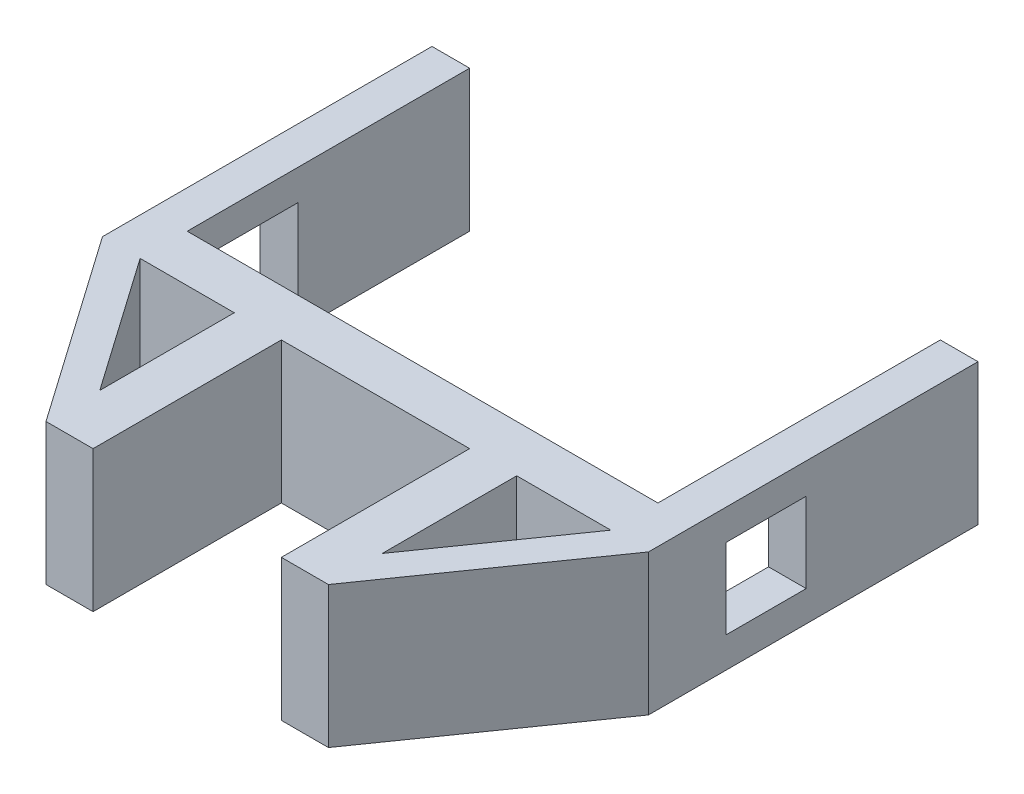
SolidWorks part; units mm, degrees
ref_plane "Front Plane" through (0, 0, 0) normal (0, 0, 1) x (1, 0, 0)
ref_plane "Top Plane" through (0, 0, 0) normal (0, 1, 0) x (1, 0, 0)
ref_plane "Right Plane" through (0, 0, 0) normal (1, 0, 0) x (0, 0, -1)
ref_axis "X" through (-88.99, 0, 0) along (1, 0, 0)
ref_axis "Y" through (0, 55, 0) along (0, -1, 0)
ref_axis "Z" through (0, 0, -88.99) along (0, 0, 1)
sketch "Sketch1" plane through (0, 0, 0) normal (0, 1, 0) x (1, 0, 0)
  line L0 (-50, 0) -> (50, 0)
  line L1 (50, 0) -> (50, 60)
  line L2 (50, 60) -> (58, 60)
  line L3 (58, 60) -> (58, -10)
  line L4 (58, -10) -> (30, -10)
  line L5 (30, -10) -> (30, -50)
  line L6 (30, -50) -> (20, -50)
  line L7 (20, -50) -> (20, -10)
  line L8 (20, -10) -> (-20, -10)
  line L9 (0, 0) -> (0, -10) construction
  line L10 (58, -10) -> (30, -50)
  line L11 (30, -38.5714) -> (50, -10)
  line L12 (-30, -38.5714) -> (-50, -10)
  line L13 (-58, -10) -> (-30, -50)
  line L14 (-20, -50) -> (-20, -10)
  line L15 (-30, -50) -> (-20, -50)
  line L16 (-30, -10) -> (-30, -50)
  line L17 (-58, -10) -> (-30, -10)
  line L18 (-58, 60) -> (-58, -10)
  line L19 (-50, 60) -> (-58, 60)
  line L20 (-50, 0) -> (-50, 60)
  point P15 (71.9459, -19.7642)
  point P16 (24.7333, -18.5818)
  point P17 (27.6346, -21.3468)
  point P28 (30.7968, -16.7781)
  point P29 (24.4198, -91.0008)
  dimension "D1" = 50
  dimension "D2" = 40
  dimension "D3" = 8
  dimension "D4" = 10
  dimension "D5" = 10
  dimension "D6" = 60
  dimension "D7" = 116
  dimension "D8" = 110
  dimension "D9" = 40
extrude "Boss-Extrude1" add sketch "Sketch1" along normal mid plane 30 contours L0 L9 L8 L7 L6 L5 L4 L3 L2 L1 | L9 L0 L20 L19 L18 L17 L16 L15 L14 L8 | L11 L5 L10 L4 | L17 L13 L16 L12 region at (-36.1233, 0, 0.3425) region at (36.1233, 0, 0.3425) region at (-42.1111, 0, 27.3016) region at (42.1111, 0, 27.3016)
sketch "Sketch2" plane through (0, 0, 0) normal (1, 0, 0) x (0, 0, -1)
  line L0 (0, 0) -> (15, 0) construction
  line L1 (6.5, 8.5) -> (23.5, 8.5)
  line L2 (6.5, 8.5) -> (6.5, -8.5)
  line L3 (6.5, -8.5) -> (23.5, -8.5)
  line L4 (23.5, 8.5) -> (23.5, -8.5)
  line L5 (6.5, 8.5) -> (23.5, -8.5) construction
  line L6 (6.5, -8.5) -> (23.5, 8.5) construction
  point P0 (15, 0)
  dimension "D1" = 17
  dimension "D2" = 15
extrude "Cut-Extrude1" cut sketch "Sketch2" against normal through all both and the other way through all
